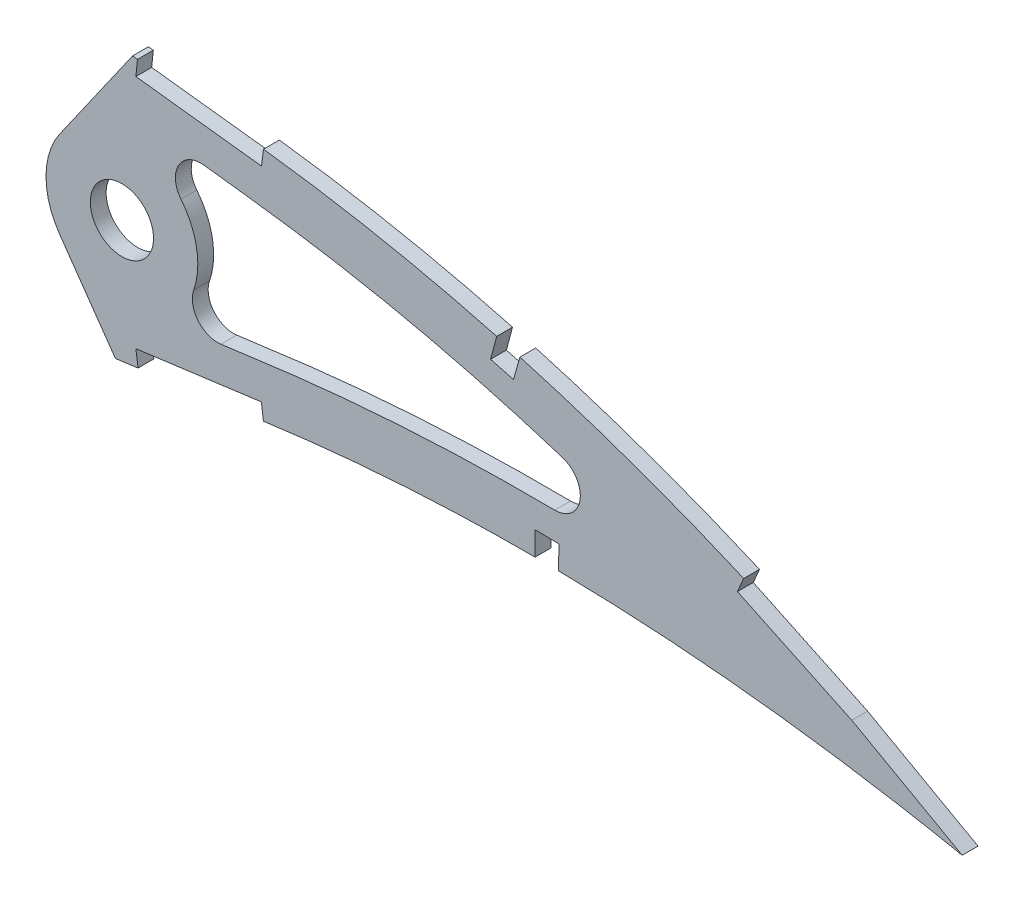
SolidWorks part; units mm, degrees
note: '?' marks a value the reader was unsure of.
material "Pine"
ref_plane "Front Plane" through (0, 0, 0) normal (0, 0, 1) x (1, 0, 0)
ref_plane "Top Plane" through (0, 0, 0) normal (0, 1, 0) x (1, 0, 0)
ref_plane "Right Plane" through (0, 0, 0) normal (1, 0, 0) x (0, 0, -1)
curve "Curve1"
  spline degree 3 poles (0, 0, 0) (0.1249, -0.5894, 0) (0.3751, -1.7709, 0) (1.0551, -3.4717, 0) (1.9543, -5.1067, 0) (3.0917, -6.6716, 0) (4.4597, -8.1658, 0) (6.0551, -9.5909, 0) (7.8766, -10.9463, 0) (9.9217, -12.2312, 0) (12.1874, -13.447, 0) (14.6712, -14.593, 0) (17.3708, -15.6688, 0) (20.2833, -16.6729, 0) (23.4051, -17.607, 0) (26.7332, -18.4687, 0) (30.2639, -19.2592, 0) (33.9938, -19.9766, 0) (37.9188, -20.6214, 0) (42.0348, -21.1935, 0) (46.3376, -21.6931, 0) (50.823, -22.1192, 0) (55.4866, -22.4726, 0) (60.3236, -22.7538, 0) (65.3294, -22.9634, 0) (70.4993, -23.1008, 0) (75.828, -23.1681, 0) (81.3109, -23.1662, 0) (86.9426, -23.0948, 0) (92.7182, -22.9577, 0) (98.6323, -22.754, 0) (104.6794, -22.4863, 0) (110.8541, -22.1572, 0) (117.1509, -21.7679, 0) (123.5642, -21.32, 0) (130.0885, -20.8172, 0) (136.7178, -20.2607, 0) (143.4464, -19.6538, 0) (150.2683, -18.9994, 0) (157.1776, -18.2998, 0) (164.1682, -17.5581, 0) (171.2339, -16.7767, 0) (178.3687, -15.9599, 0) (185.566, -15.1091, 0) (192.8198, -14.2292, 0) (200.1233, -13.3218, 0) (207.4703, -12.3905, 0) (214.8542, -11.4396, 0) (222.2681, -10.469, 0) (229.7058, -9.4856, 0) (237.1601, -8.4887, 0) (244.6246, -7.4833, 0) (252.0922, -6.4726, 0) (259.5558, -5.4569, 0) (267.0088, -4.4404, 0) (274.4442, -3.4259, 0) (281.8548, -2.4135, 0) (289.2339, -1.4081, 0) (296.574, -0.4098, 0) (303.8684, 0.5795, 0) (311.1101, 1.5569, 0) (318.2922, 2.521, 0) (325.4074, 3.4714, 0) (332.4485, 4.4082, 0) (339.3029, 5.3032, 0) (345.9529, 6.204, 0) (352.4207, 6.9424, 0) (358.808, 7.5727, 0) (365.1214, 8.0894, 0) (371.3533, 8.5001, 0) (377.4966, 8.8075, 0) (383.544, 9.0161, 0) (389.4878, 9.132, 0) (395.3205, 9.1582, 0) (401.0343, 9.1029, 0) (406.6218, 8.9708, 0) (412.075, 8.7675, 0) (417.3864, 8.5002, 0) (422.5485, 8.1759, 0) (427.5535, 7.7996, 0) (432.3944, 7.38, 0) (437.0637, 6.9232, 0) (441.5544, 6.4344, 0) (445.8598, 5.924, 0) (449.973, 5.3952, 0) (453.8879, 4.8568, 0) (457.5982, 4.3142, 0) (461.0979, 3.7743, 0) (464.3817, 3.2423, 0) (467.4441, 2.7253, 0) (470.2803, 2.228, 0) (472.8856, 1.7553, 0) (475.2562, 1.3133, 0) (477.3874, 0.904, 0) (479.2765, 0.5343, 0) (480.9199, 0.2058, 0) (482.3151, -0.077, 0) (483.4599, -0.3128, 0) (484.3523, -0.4979, 0) (484.9907, -0.6325, 0) (485.3743, -0.7125, 0) (485.5448, -0.7489, 0) (485.5874, -0.758, 0) knots 0 0 0 0 0.003638 0.007293 0.011028 0.014901 0.018963 0.023258 0.027821 0.032679 0.037853 0.043362 0.049215 0.055422 0.061989 0.068918 0.076211 0.083868 0.091887 0.100266 0.109 0.118085 0.127515 0.137285 0.147388 0.157816 0.168563 0.179619 0.190977 0.202627 0.21456 0.226767 0.239236 0.251959 0.264924 0.27812 0.291536 0.30516 0.318981 0.332985 0.347163 0.361499 0.375981 0.390597 0.405333 0.420175 0.43511 0.450124 0.465203 0.480333 0.495501 0.51069 0.525887 0.541078 0.556247 0.571382 0.586466 0.601485 0.616424 0.631269 0.646007 0.660621 0.675098 0.689423 0.703582 0.716908 0.730009 0.742952 0.755726 0.76832 0.780724 0.792927 0.804916 0.816679 0.828204 0.839475 0.850481 0.861208 0.871639 0.881763 0.891564 0.901027 0.910139 0.918884 0.927249 0.935221 0.942785 0.949928 0.956638 0.962904 0.968712 0.974054 0.978918 0.983297 0.98718 0.990561 0.993433 0.995791 0.99763 0.998946 0.999737 1 1 1 1
curve "Curve2"
  spline degree 3 poles (486.1938, 0.758, 0) (486.1565, 0.781, 0) (486.0077, 0.8729, 0) (485.6723, 1.0786, 0) (485.1139, 1.4213, 0) (484.3321, 1.8984, 0) (483.3276, 2.5088, 0) (482.0999, 3.2482, 0) (480.6498, 4.1141, 0) (478.9775, 5.1026, 0) (477.0833, 6.2089, 0) (474.9678, 7.4286, 0) (472.6313, 8.7548, 0) (470.0748, 10.182, 0) (467.2989, 11.7035, 0) (464.3043, 13.3123, 0) (461.0921, 15.0004, 0) (457.6635, 16.7605, 0) (454.019, 18.5827, 0) (450.1605, 20.4596, 0) (446.0892, 22.3819, 0) (441.8065, 24.3391, 0) (437.3149, 26.3234, 0) (432.6155, 28.3224, 0) (427.7112, 30.3274, 0) (422.6039, 32.3272, 0) (417.2967, 34.3124, 0) (411.7916, 36.2703, 0) (406.0928, 38.1924, 0) (400.203, 40.0661, 0) (394.1264, 41.8812, 0) (387.8666, 43.626, 0) (381.4288, 45.2916, 0) (374.8171, 46.8658, 0) (368.037, 48.3381, 0) (361.0939, 49.6996, 0) (353.9938, 50.9366, 0) (346.7562, 52.0484, 0) (339.4976, 52.9732, 0) (332.2539, 53.8802, 0) (325.021, 54.7322, 0) (317.6998, 55.5482, 0) (310.2971, 56.3235, 0) (302.8205, 57.0556, 0) (295.2774, 57.7415, 0) (287.6757, 58.3791, 0) (280.0227, 58.9648, 0) (272.3266, 59.4977, 0) (264.5949, 59.9731, 0) (256.8359, 60.3907, 0) (249.0573, 60.7475, 0) (241.2675, 61.0411, 0) (233.4745, 61.2698, 0) (225.6865, 61.4312, 0) (217.912, 61.5245, 0) (210.159, 61.547, 0) (202.4359, 61.4984, 0) (194.7508, 61.377, 0) (187.1122, 61.1811, 0) (179.5282, 60.9103, 0) (172.0069, 60.5649, 0) (164.5567, 60.1418, 0) (157.1855, 59.6438, 0) (149.9016, 59.0688, 0) (142.713, 58.4167, 0) (135.6273, 57.6901, 0) (128.6522, 56.887, 0) (121.7954, 56.0099, 0) (115.0642, 55.0603, 0) (108.4663, 54.0378, 0) (102.0087, 52.9453, 0) (95.6983, 51.784, 0) (89.542, 50.5572, 0) (83.5463, 49.2652, 0) (77.7176, 47.912, 0) (72.062, 46.4999, 0) (66.5855, 45.0315, 0) (61.2937, 43.5103, 0) (56.192, 41.9397, 0) (51.2862, 40.3215, 0) (46.5802, 38.6618, 0) (42.0796, 36.9619, 0) (37.788, 35.2268, 0) (33.7103, 33.4591, 0) (29.8497, 31.6641, 0) (26.2104, 29.8437, 0) (22.7951, 28.0033, 0) (19.6072, 26.1454, 0) (16.6497, 24.2737, 0) (13.924, 22.3929, 0) (11.4337, 20.504, 0) (9.1798, 18.612, 0) (7.1636, 16.7197, 0) (5.388, 14.8284, 0) (3.8531, 12.9414, 0) (2.5606, 11.0602, 0) (1.511, 9.1866, 0) (0.7066, 7.3219, 0) (0.1466, 5.4673, 0) (-0.16, 3.6254, 0) (-0.2363, 1.7948, 0) (-0.0786, 0.5974, 0) (0, 0, 0) knots 0 0 0 0 0.000254 0.001015 0.002283 0.004057 0.006331 0.009105 0.012374 0.016134 0.02038 0.025106 0.030306 0.035972 0.0421 0.048678 0.055702 0.06316 0.071046 0.07935 0.088063 0.097176 0.106678 0.116562 0.126814 0.137428 0.148394 0.1597 0.171338 0.183298 0.19557 0.208144 0.221012 0.234162 0.247587 0.261277 0.275223 0.289414 0.303771 0.317689 0.331784 0.34604 0.360444 0.374983 0.38964 0.404403 0.419257 0.434187 0.449177 0.464215 0.479284 0.49437 0.509458 0.524532 0.539579 0.554583 0.56953 0.584403 0.599191 0.613877 0.628447 0.642889 0.657186 0.671326 0.685294 0.699078 0.712665 0.726043 0.739198 0.752118 0.764792 0.777208 0.789356 0.801224 0.812804 0.824083 0.835055 0.84571 0.856038 0.866034 0.875689 0.884998 0.893953 0.902553 0.910789 0.918661 0.926166 0.933303 0.940071 0.946475 0.952518 0.958205 0.963547 0.968557 0.97325 0.977651 0.981787 0.985694 0.989415 0.993001 0.996508 1 1 1 1
sketch "Sketch1" plane through (0, 0, 0) normal (0, 0, 1) x (1, 0, 0)
  line L10 (485.5874, -0.758) -> (490.1477, -1.6846)
  line L24 (486.1938, 0.758) -> (490.1477, -1.6846)
  spline S2 degree 3 poles (-2903.3012, -752.343) (64.9845, 66.2759) (-8.319, 19.9761) (1.0551, -3.4717) (1.9543, -5.1067) (3.0917, -6.6716) (4.4597, -8.1658) (6.0551, -9.5909) (7.8766, -10.9463) (9.9217, -12.2312) (12.1874, -13.447) (14.6712, -14.593) (17.3708, -15.6688) (20.2833, -16.6729) (23.4051, -17.607) (26.7332, -18.4687) (30.2639, -19.2592) (33.9938, -19.9766) (37.9188, -20.6214) (42.0348, -21.1935) (46.3376, -21.6931) (50.823, -22.1192) (55.4866, -22.4726) (60.3236, -22.7538) (65.3294, -22.9634) (70.4993, -23.1008) (75.828, -23.1681) (81.3109, -23.1662) (86.9426, -23.0948) (92.7182, -22.9577) (98.6323, -22.754) (104.6794, -22.4863) (110.8541, -22.1572) (117.1509, -21.7679) (123.5642, -21.32) (130.0885, -20.8172) (136.7178, -20.2607) (143.4464, -19.6538) (150.2683, -18.9994) (157.1776, -18.2998) (164.1682, -17.5581) (171.2339, -16.7767) (178.3687, -15.9599) (185.566, -15.1091) (192.8198, -14.2292) (200.1233, -13.3218) (207.4703, -12.3905) (214.8542, -11.4396) (222.2681, -10.469) (229.7058, -9.4856) (237.1601, -8.4887) (244.6246, -7.4833) (252.0922, -6.4726) (259.5558, -5.4569) (267.0088, -4.4404) (274.4442, -3.4259) (281.8548, -2.4135) (289.2339, -1.4081) (296.574, -0.4098) (303.8684, 0.5795) (311.1101, 1.5569) (318.2922, 2.521) (325.4074, 3.4714) (332.4485, 4.4082) (339.3029, 5.3032) (345.9529, 6.204) (352.4207, 6.9424) (358.808, 7.5727) (365.1214, 8.0894) (371.3533, 8.5001) (377.4966, 8.8075) (383.544, 9.0161) (389.4878, 9.132) (395.3205, 9.1582) (401.0343, 9.1029) (406.6218, 8.9708) (412.075, 8.7675) (417.3864, 8.5002) (422.5485, 8.1759) (427.5535, 7.7996) (432.3944, 7.38) (437.0637, 6.9232) (441.5544, 6.4344) (445.8598, 5.924) (449.973, 5.3952) (453.8879, 4.8568) (457.5982, 4.3142) (461.0979, 3.7743) (464.3817, 3.2423) (467.4441, 2.7253) (470.2803, 2.228) (472.8856, 1.7553) (475.2562, 1.3133) (477.3874, 0.904) (479.2765, 0.5343) (480.9199, 0.2058) (482.3151, -0.077) (483.4599, -0.3128) (484.3523, -0.4979) (484.9907, -0.6325) (502.3108, -4.2475) (517.8244, -15.3527) (1156.8132, 2922.2173) knots -0.141005 -0.141005 -0.141005 -0.141005 0.003638 0.007293 0.011028 0.014901 0.018963 0.023258 0.027821 0.032679 0.037853 0.043362 0.049215 0.055422 0.061989 0.068918 0.076211 0.083868 0.091887 0.100266 0.109 0.118085 0.127515 0.137285 0.147388 0.157816 0.168563 0.179619 0.190977 0.202627 0.21456 0.226767 0.239236 0.251959 0.264924 0.27812 0.291536 0.30516 0.318981 0.332985 0.347163 0.361499 0.375981 0.390597 0.405333 0.420175 0.43511 0.450124 0.465203 0.480333 0.495501 0.51069 0.525887 0.541078 0.556247 0.571382 0.586466 0.601485 0.616424 0.631269 0.646007 0.660621 0.675098 0.689423 0.703582 0.716908 0.730009 0.742952 0.755726 0.76832 0.780724 0.792927 0.804916 0.816679 0.828204 0.839475 0.850481 0.861208 0.871639 0.881763 0.891564 0.901027 0.910139 0.918884 0.927249 0.935221 0.942785 0.949928 0.956638 0.962904 0.968712 0.974054 0.978918 0.983297 0.98718 0.990561 0.993433 0.995791 0.99763 0.998946 0.999737 1.104643 1.104643 1.104643 1.104643 only from (0, 0) to (485.5874, -0.758) construction
  spline S3 degree 3 poles (2108.3155, 2523.1468) (515.5269, -25.3358) (502.504, -9.2456) (485.6723, 1.0786) (485.1139, 1.4213) (484.3321, 1.8984) (483.3276, 2.5088) (482.0999, 3.2482) (480.6498, 4.1141) (478.9775, 5.1026) (477.0833, 6.2089) (474.9678, 7.4286) (472.6313, 8.7548) (470.0748, 10.182) (467.2989, 11.7035) (464.3043, 13.3123) (461.0921, 15.0004) (457.6635, 16.7605) (454.019, 18.5827) (450.1605, 20.4596) (446.0892, 22.3819) (441.8065, 24.3391) (437.3149, 26.3234) (432.6155, 28.3224) (427.7112, 30.3274) (422.6039, 32.3272) (417.2967, 34.3124) (411.7916, 36.2703) (406.0928, 38.1924) (400.203, 40.0661) (394.1264, 41.8812) (387.8666, 43.626) (381.4288, 45.2916) (374.8171, 46.8658) (368.037, 48.3381) (361.0939, 49.6996) (353.9938, 50.9366) (346.7562, 52.0484) (339.4976, 52.9732) (332.2539, 53.8802) (325.021, 54.7322) (317.6998, 55.5482) (310.2971, 56.3235) (302.8205, 57.0556) (295.2774, 57.7415) (287.6757, 58.3791) (280.0227, 58.9648) (272.3266, 59.4977) (264.5949, 59.9731) (256.8359, 60.3907) (249.0573, 60.7475) (241.2675, 61.0411) (233.4745, 61.2698) (225.6865, 61.4312) (217.912, 61.5245) (210.159, 61.547) (202.4359, 61.4984) (194.7508, 61.377) (187.1122, 61.1811) (179.5282, 60.9103) (172.0069, 60.5649) (164.5567, 60.1418) (157.1855, 59.6438) (149.9016, 59.0688) (142.713, 58.4167) (135.6273, 57.6901) (128.6522, 56.887) (121.7954, 56.0099) (115.0642, 55.0603) (108.4663, 54.0378) (102.0087, 52.9453) (95.6983, 51.784) (89.542, 50.5572) (83.5463, 49.2652) (77.7176, 47.912) (72.062, 46.4999) (66.5855, 45.0315) (61.2937, 43.5103) (56.192, 41.9397) (51.2862, 40.3215) (46.5802, 38.6618) (42.0796, 36.9619) (37.788, 35.2268) (33.7103, 33.4591) (29.8497, 31.6641) (26.2104, 29.8437) (22.7951, 28.0033) (19.6072, 26.1454) (16.6497, 24.2737) (13.924, 22.3929) (11.4337, 20.504) (9.1798, 18.612) (7.1636, 16.7197) (5.388, 14.8284) (3.8531, 12.9414) (2.5606, 11.0602) (1.511, 9.1866) (0.7066, 7.3219) (0.1466, 5.4673) (-0.16, 3.6254) (-1.2099, -21.5622) (83.495, -40.781) (-2988.1493, -256.3193) knots -0.112318 -0.112318 -0.112318 -0.112318 0.000254 0.001015 0.002283 0.004057 0.006331 0.009105 0.012374 0.016134 0.02038 0.025106 0.030306 0.035972 0.0421 0.048678 0.055702 0.06316 0.071046 0.07935 0.088063 0.097176 0.106678 0.116562 0.126814 0.137428 0.148394 0.1597 0.171338 0.183298 0.19557 0.208144 0.221012 0.234162 0.247587 0.261277 0.275223 0.289414 0.303771 0.317689 0.331784 0.34604 0.360444 0.374983 0.38964 0.404403 0.419257 0.434187 0.449177 0.464215 0.479284 0.49437 0.509458 0.524532 0.539579 0.554583 0.56953 0.584403 0.599191 0.613877 0.628447 0.642889 0.657186 0.671326 0.685294 0.699078 0.712665 0.726043 0.739198 0.752118 0.764792 0.777208 0.789356 0.801224 0.812804 0.824083 0.835055 0.84571 0.856038 0.866034 0.875689 0.884998 0.893953 0.902553 0.910789 0.918661 0.926166 0.933303 0.940071 0.946475 0.952518 0.958205 0.963547 0.968557 0.97325 0.977651 0.981787 0.985694 0.989415 0.993001 0.996508 1.135054 1.135054 1.135054 1.135054 only from (486.1938, 0.758) to (0, 0) construction
  spline S4 degree 3 poles (0, 0) (0.1249, -0.5894) (0.3751, -1.7709) (1.0551, -3.4717) (1.9543, -5.1067) (3.0917, -6.6716) (4.4597, -8.1658) (6.0551, -9.5909) (7.8766, -10.9463) (9.9217, -12.2312) (12.1874, -13.447) (14.6712, -14.593) (17.3708, -15.6688) (20.2833, -16.6729) (23.4051, -17.607) (26.7332, -18.4687) (30.2639, -19.2592) (33.9938, -19.9766) (37.9188, -20.6214) (42.0348, -21.1935) (46.3376, -21.6931) (50.823, -22.1192) (55.4866, -22.4726) (60.3236, -22.7538) (65.3294, -22.9634) (70.4993, -23.1008) (75.828, -23.1681) (81.3109, -23.1662) (86.9426, -23.0948) (92.7182, -22.9577) (98.6323, -22.754) (104.6794, -22.4863) (110.8541, -22.1572) (117.1509, -21.7679) (123.5642, -21.32) (130.0885, -20.8172) (136.7178, -20.2607) (143.4464, -19.6538) (150.2683, -18.9994) (157.1776, -18.2998) (164.1682, -17.5581) (171.2339, -16.7767) (178.3687, -15.9599) (185.566, -15.1091) (192.8198, -14.2292) (200.1233, -13.3218) (207.4703, -12.3905) (214.8542, -11.4396) (222.2681, -10.469) (229.7058, -9.4856) (237.1601, -8.4887) (244.6246, -7.4833) (252.0922, -6.4726) (259.5558, -5.4569) (267.0088, -4.4404) (274.4442, -3.4259) (281.8548, -2.4135) (289.2339, -1.4081) (296.574, -0.4098) (303.8684, 0.5795) (311.1101, 1.5569) (318.2922, 2.521) (325.4074, 3.4714) (332.4485, 4.4082) (339.3029, 5.3032) (345.9529, 6.204) (352.4207, 6.9424) (358.808, 7.5727) (365.1214, 8.0894) (371.3533, 8.5001) (377.4966, 8.8075) (383.544, 9.0161) (389.4878, 9.132) (395.3205, 9.1582) (401.0343, 9.1029) (406.6218, 8.9708) (412.075, 8.7675) (417.3864, 8.5002) (422.5485, 8.1759) (427.5535, 7.7996) (432.3944, 7.38) (437.0637, 6.9232) (441.5544, 6.4344) (445.8598, 5.924) (449.973, 5.3952) (453.8879, 4.8568) (457.5982, 4.3142) (461.0979, 3.7743) (464.3817, 3.2423) (467.4441, 2.7253) (470.2803, 2.228) (472.8856, 1.7553) (475.2562, 1.3133) (477.3874, 0.904) (479.2765, 0.5343) (480.9199, 0.2058) (482.3151, -0.077) (483.4599, -0.3128) (484.3523, -0.4979) (484.9907, -0.6325) (485.3743, -0.7125) (485.5448, -0.7489) (485.5874, -0.758) knots 0 0 0 0 0.003638 0.007293 0.011028 0.014901 0.018963 0.023258 0.027821 0.032679 0.037853 0.043362 0.049215 0.055422 0.061989 0.068918 0.076211 0.083868 0.091887 0.100266 0.109 0.118085 0.127515 0.137285 0.147388 0.157816 0.168563 0.179619 0.190977 0.202627 0.21456 0.226767 0.239236 0.251959 0.264924 0.27812 0.291536 0.30516 0.318981 0.332985 0.347163 0.361499 0.375981 0.390597 0.405333 0.420175 0.43511 0.450124 0.465203 0.480333 0.495501 0.51069 0.525887 0.541078 0.556247 0.571382 0.586466 0.601485 0.616424 0.631269 0.646007 0.660621 0.675098 0.689423 0.703582 0.716908 0.730009 0.742952 0.755726 0.76832 0.780724 0.792927 0.804916 0.816679 0.828204 0.839475 0.850481 0.861208 0.871639 0.881763 0.891564 0.901027 0.910139 0.918884 0.927249 0.935221 0.942785 0.949928 0.956638 0.962904 0.968712 0.974054 0.978918 0.983297 0.98718 0.990561 0.993433 0.995791 0.99763 0.998946 0.999737 1 1 1 1
  spline S5 degree 3 poles (486.1938, 0.758) (486.1565, 0.781) (486.0077, 0.8729) (485.6723, 1.0786) (485.1139, 1.4213) (484.3321, 1.8984) (483.3276, 2.5088) (482.0999, 3.2482) (480.6498, 4.1141) (478.9775, 5.1026) (477.0833, 6.2089) (474.9678, 7.4286) (472.6313, 8.7548) (470.0748, 10.182) (467.2989, 11.7035) (464.3043, 13.3123) (461.0921, 15.0004) (457.6635, 16.7605) (454.019, 18.5827) (450.1605, 20.4596) (446.0892, 22.3819) (441.8065, 24.3391) (437.3149, 26.3234) (432.6155, 28.3224) (427.7112, 30.3274) (422.6039, 32.3272) (417.2967, 34.3124) (411.7916, 36.2703) (406.0928, 38.1924) (400.203, 40.0661) (394.1264, 41.8812) (387.8666, 43.626) (381.4288, 45.2916) (374.8171, 46.8658) (368.037, 48.3381) (361.0939, 49.6996) (353.9938, 50.9366) (346.7562, 52.0484) (339.4976, 52.9732) (332.2539, 53.8802) (325.021, 54.7322) (317.6998, 55.5482) (310.2971, 56.3235) (302.8205, 57.0556) (295.2774, 57.7415) (287.6757, 58.3791) (280.0227, 58.9648) (272.3266, 59.4977) (264.5949, 59.9731) (256.8359, 60.3907) (249.0573, 60.7475) (241.2675, 61.0411) (233.4745, 61.2698) (225.6865, 61.4312) (217.912, 61.5245) (210.159, 61.547) (202.4359, 61.4984) (194.7508, 61.377) (187.1122, 61.1811) (179.5282, 60.9103) (172.0069, 60.5649) (164.5567, 60.1418) (157.1855, 59.6438) (149.9016, 59.0688) (142.713, 58.4167) (135.6273, 57.6901) (128.6522, 56.887) (121.7954, 56.0099) (115.0642, 55.0603) (108.4663, 54.0378) (102.0087, 52.9453) (95.6983, 51.784) (89.542, 50.5572) (83.5463, 49.2652) (77.7176, 47.912) (72.062, 46.4999) (66.5855, 45.0315) (61.2937, 43.5103) (56.192, 41.9397) (51.2862, 40.3215) (46.5802, 38.6618) (42.0796, 36.9619) (37.788, 35.2268) (33.7103, 33.4591) (29.8497, 31.6641) (26.2104, 29.8437) (22.7951, 28.0033) (19.6072, 26.1454) (16.6497, 24.2737) (13.924, 22.3929) (11.4337, 20.504) (9.1798, 18.612) (7.1636, 16.7197) (5.388, 14.8284) (3.8531, 12.9414) (2.5606, 11.0602) (1.511, 9.1866) (0.7066, 7.3219) (0.1466, 5.4673) (-0.16, 3.6254) (-0.2363, 1.7948) (-0.0786, 0.5974) (0, 0) knots 0 0 0 0 0.000254 0.001015 0.002283 0.004057 0.006331 0.009105 0.012374 0.016134 0.02038 0.025106 0.030306 0.035972 0.0421 0.048678 0.055702 0.06316 0.071046 0.07935 0.088063 0.097176 0.106678 0.116562 0.126814 0.137428 0.148394 0.1597 0.171338 0.183298 0.19557 0.208144 0.221012 0.234162 0.247587 0.261277 0.275223 0.289414 0.303771 0.317689 0.331784 0.34604 0.360444 0.374983 0.38964 0.404403 0.419257 0.434187 0.449177 0.464215 0.479284 0.49437 0.509458 0.524532 0.539579 0.554583 0.56953 0.584403 0.599191 0.613877 0.628447 0.642889 0.657186 0.671326 0.685294 0.699078 0.712665 0.726043 0.739198 0.752118 0.764792 0.777208 0.789356 0.801224 0.812804 0.824083 0.835055 0.84571 0.856038 0.866034 0.875689 0.884998 0.893953 0.902553 0.910789 0.918661 0.926166 0.933303 0.940071 0.946475 0.952518 0.958205 0.963547 0.968557 0.97325 0.977651 0.981787 0.985694 0.989415 0.993001 0.996508 1 1 1 1
extrude "Boss-Extrude1" add sketch "Sketch1" along normal blind 3.175
sketch "Sketch3" plane through (0, 0, 0) normal (0, 0, -1) x (-1, 0, 0)
  circle A0 centre (-312.3477, 26.2554) radius 6.35
  dimension "D1" = 12.7
  dimension "D2" = 177.8
  dimension "D3" = 27.94
extrude "Cut-Extrude2" cut sketch "Sketch3" against normal blind 7.62 contours A0
sketch "Sketch4" plane through (0, 0, 3.175) normal (0, 0, 1) x (1, 0, 0)
  line L0 (299.8639, 34.9967) -> (314.4881, 55.8824)
  line L1 (299.8639, 17.5141) -> (311.0441, 1.5471)
  line L2 (312.3477, 26.2554) -> (351.4914, 26.2554) construction
  line L3 (315.4787, 55.7778) -> (315.1439, 52.6205)
  line L4 (315.1439, 52.6205) -> (340.3707, 49.6596)
  line L5 (340.3707, 49.6596) -> (340.7711, 52.8093)
  line L6 (315.5809, 2.1568) -> (315.1587, 5.3036)
  line L7 (315.1587, 5.3036) -> (340.3373, 8.6498)
  line L8 (340.3373, 8.6498) -> (340.7575, 5.5027)
  line L9 (482.6749, 2.9016) -> (481.0376, 0.1814)
  line L10 (481.0376, 0.1814) -> (458.8647, 12.5718)
  line L11 (458.8647, 12.5718) -> (435.9153, 23.457)
  line L12 (435.9153, 23.457) -> (437.177, 26.3706)
  line L13 (458.8647, 12.5718) -> (460.3217, 15.3927)
  line L14 (387.5921, 43.6785) -> (386.3601, 39.0781)
  line L15 (386.3601, 39.0781) -> (390.9605, 37.8461)
  line L16 (390.9605, 37.8461) -> (392.2468, 42.3976)
  line L17 (395.3015, 9.1446) -> (395.3135, 13.9071)
  line L18 (395.3135, 13.9071) -> (400.0755, 13.8399)
  line L19 (400.0755, 13.8399) -> (400.0088, 9.1055)
  line L20 (437.177, 26.3706) -> (392.2468, 42.3976) construction
  line L21 (387.5921, 43.6785) -> (340.7711, 52.8093) construction
  line L22 (458.8647, 12.5718) -> (454.5015, 4.7638)
  line L23 (454.5015, 4.7638) -> (400.0088, 9.1055) construction
  line L24 (395.3015, 9.1446) -> (340.7575, 5.5027) construction
  circle A0 centre (312.3477, 26.2554) radius 6.35 construction
  circle A1 centre (312.3477, 26.2554) radius 6.35
  circle A2 centre (312.3477, 26.2554) radius 15.24
  arc A3 (324.2094, 35.8241) -> (328.7645, 44.0579) centre (328.1632, 39.0136) cw
  spline S0 degree 3 poles (-2903.3012, -752.343) (64.9845, 66.2759) (-8.319, 19.9761) (1.0551, -3.4717) (1.9543, -5.1067) (3.0917, -6.6716) (4.4597, -8.1658) (6.0551, -9.5909) (7.8766, -10.9463) (9.9217, -12.2312) (12.1874, -13.447) (14.6712, -14.593) (17.3708, -15.6688) (20.2833, -16.6729) (23.4051, -17.607) (26.7332, -18.4687) (30.2639, -19.2592) (33.9938, -19.9766) (37.9188, -20.6214) (42.0348, -21.1935) (46.3376, -21.6931) (50.823, -22.1192) (55.4866, -22.4726) (60.3236, -22.7538) (65.3294, -22.9634) (70.4993, -23.1008) (75.828, -23.1681) (81.3109, -23.1662) (86.9426, -23.0948) (92.7182, -22.9577) (98.6323, -22.754) (104.6794, -22.4863) (110.8541, -22.1572) (117.1509, -21.7679) (123.5642, -21.32) (130.0885, -20.8172) (136.7178, -20.2607) (143.4464, -19.6538) (150.2683, -18.9994) (157.1776, -18.2998) (164.1682, -17.5581) (171.2339, -16.7767) (178.3687, -15.9599) (185.566, -15.1091) (192.8198, -14.2292) (200.1233, -13.3218) (207.4703, -12.3905) (214.8542, -11.4396) (222.2681, -10.469) (229.7058, -9.4856) (237.1601, -8.4887) (244.6246, -7.4833) (252.0922, -6.4726) (259.5558, -5.4569) (267.0088, -4.4404) (274.4442, -3.4259) (281.8548, -2.4135) (289.2339, -1.4081) (296.574, -0.4098) (303.8684, 0.5795) (311.1101, 1.5569) (318.2922, 2.521) (325.4074, 3.4714) (332.4485, 4.4082) (339.3029, 5.3032) (345.9529, 6.204) (352.4207, 6.9424) (358.808, 7.5727) (365.1214, 8.0894) (371.3533, 8.5001) (377.4966, 8.8075) (383.544, 9.0161) (389.4878, 9.132) (395.3205, 9.1582) (401.0343, 9.1029) (406.6218, 8.9708) (412.075, 8.7675) (417.3864, 8.5002) (422.5485, 8.1759) (427.5535, 7.7996) (432.3944, 7.38) (437.0637, 6.9232) (441.5544, 6.4344) (445.8598, 5.924) (449.973, 5.3952) (453.8879, 4.8568) (457.5982, 4.3142) (461.0979, 3.7743) (464.3817, 3.2423) (467.4441, 2.7253) (470.2803, 2.228) (472.8856, 1.7553) (475.2562, 1.3133) (477.3874, 0.904) (479.2765, 0.5343) (480.9199, 0.2058) (482.3151, -0.077) (483.4599, -0.3128) (484.3523, -0.4979) (484.9907, -0.6325) (502.3108, -4.2475) (517.8244, -15.3527) (1156.8132, 2922.2173) knots -0.141005 -0.141005 -0.141005 -0.141005 0.003638 0.007293 0.011028 0.014901 0.018963 0.023258 0.027821 0.032679 0.037853 0.043362 0.049215 0.055422 0.061989 0.068918 0.076211 0.083868 0.091887 0.100266 0.109 0.118085 0.127515 0.137285 0.147388 0.157816 0.168563 0.179619 0.190977 0.202627 0.21456 0.226767 0.239236 0.251959 0.264924 0.27812 0.291536 0.30516 0.318981 0.332985 0.347163 0.361499 0.375981 0.390597 0.405333 0.420175 0.43511 0.450124 0.465203 0.480333 0.495501 0.51069 0.525887 0.541078 0.556247 0.571382 0.586466 0.601485 0.616424 0.631269 0.646007 0.660621 0.675098 0.689423 0.703582 0.716908 0.730009 0.742952 0.755726 0.76832 0.780724 0.792927 0.804916 0.816679 0.828204 0.839475 0.850481 0.861208 0.871639 0.881763 0.891564 0.901027 0.910139 0.918884 0.927249 0.935221 0.942785 0.949928 0.956638 0.962904 0.968712 0.974054 0.978918 0.983297 0.98718 0.990561 0.993433 0.995791 0.99763 0.998946 0.999737 1.104643 1.104643 1.104643 1.104643 only from (0, 0) to (485.5874, -0.758) construction
  spline S1 degree 3 poles (2108.3155, 2523.1468) (515.5269, -25.3358) (502.504, -9.2456) (485.6723, 1.0786) (485.1139, 1.4213) (484.3321, 1.8984) (483.3276, 2.5088) (482.0999, 3.2482) (480.6498, 4.1141) (478.9775, 5.1026) (477.0833, 6.2089) (474.9678, 7.4286) (472.6313, 8.7548) (470.0748, 10.182) (467.2989, 11.7035) (464.3043, 13.3123) (461.0921, 15.0004) (457.6635, 16.7605) (454.019, 18.5827) (450.1605, 20.4596) (446.0892, 22.3819) (441.8065, 24.3391) (437.3149, 26.3234) (432.6155, 28.3224) (427.7112, 30.3274) (422.6039, 32.3272) (417.2967, 34.3124) (411.7916, 36.2703) (406.0928, 38.1924) (400.203, 40.0661) (394.1264, 41.8812) (387.8666, 43.626) (381.4288, 45.2916) (374.8171, 46.8658) (368.037, 48.3381) (361.0939, 49.6996) (353.9938, 50.9366) (346.7562, 52.0484) (339.4976, 52.9732) (332.2539, 53.8802) (325.021, 54.7322) (317.6998, 55.5482) (310.2971, 56.3235) (302.8205, 57.0556) (295.2774, 57.7415) (287.6757, 58.3791) (280.0227, 58.9648) (272.3266, 59.4977) (264.5949, 59.9731) (256.8359, 60.3907) (249.0573, 60.7475) (241.2675, 61.0411) (233.4745, 61.2698) (225.6865, 61.4312) (217.912, 61.5245) (210.159, 61.547) (202.4359, 61.4984) (194.7508, 61.377) (187.1122, 61.1811) (179.5282, 60.9103) (172.0069, 60.5649) (164.5567, 60.1418) (157.1855, 59.6438) (149.9016, 59.0688) (142.713, 58.4167) (135.6273, 57.6901) (128.6522, 56.887) (121.7954, 56.0099) (115.0642, 55.0603) (108.4663, 54.0378) (102.0087, 52.9453) (95.6983, 51.784) (89.542, 50.5572) (83.5463, 49.2652) (77.7176, 47.912) (72.062, 46.4999) (66.5855, 45.0315) (61.2937, 43.5103) (56.192, 41.9397) (51.2862, 40.3215) (46.5802, 38.6618) (42.0796, 36.9619) (37.788, 35.2268) (33.7103, 33.4591) (29.8497, 31.6641) (26.2104, 29.8437) (22.7951, 28.0033) (19.6072, 26.1454) (16.6497, 24.2737) (13.924, 22.3929) (11.4337, 20.504) (9.1798, 18.612) (7.1636, 16.7197) (5.388, 14.8284) (3.8531, 12.9414) (2.5606, 11.0602) (1.511, 9.1866) (0.7066, 7.3219) (0.1466, 5.4673) (-0.16, 3.6254) (-1.2099, -21.5622) (83.495, -40.781) (-2988.1493, -256.3193) knots -0.112318 -0.112318 -0.112318 -0.112318 0.000254 0.001015 0.002283 0.004057 0.006331 0.009105 0.012374 0.016134 0.02038 0.025106 0.030306 0.035972 0.0421 0.048678 0.055702 0.06316 0.071046 0.07935 0.088063 0.097176 0.106678 0.116562 0.126814 0.137428 0.148394 0.1597 0.171338 0.183298 0.19557 0.208144 0.221012 0.234162 0.247587 0.261277 0.275223 0.289414 0.303771 0.317689 0.331784 0.34604 0.360444 0.374983 0.38964 0.404403 0.419257 0.434187 0.449177 0.464215 0.479284 0.49437 0.509458 0.524532 0.539579 0.554583 0.56953 0.584403 0.599191 0.613877 0.628447 0.642889 0.657186 0.671326 0.685294 0.699078 0.712665 0.726043 0.739198 0.752118 0.764792 0.777208 0.789356 0.801224 0.812804 0.824083 0.835055 0.84571 0.856038 0.866034 0.875689 0.884998 0.893953 0.902553 0.910789 0.918661 0.926166 0.933303 0.940071 0.946475 0.952518 0.958205 0.963547 0.968557 0.97325 0.977651 0.981787 0.985694 0.989415 0.993001 0.996508 1.135054 1.135054 1.135054 1.135054 only from (486.1938, 0.758) to (0, 0) construction
  spline S2 degree 3 poles (175.8391, -16.2481) (176.6748, -16.152) (179.9112, -15.7776) (185.566, -15.1091) (192.8198, -14.2292) (200.1233, -13.3218) (207.4703, -12.3905) (214.8542, -11.4396) (222.2681, -10.469) (229.7058, -9.4856) (237.1601, -8.4887) (244.6246, -7.4833) (252.0922, -6.4726) (259.5558, -5.4569) (267.0088, -4.4404) (274.4442, -3.4259) (281.8548, -2.4135) (289.2339, -1.4081) (296.574, -0.4098) (303.8684, 0.5795) (311.1101, 1.5569) (318.2922, 2.521) (325.4074, 3.4714) (332.4485, 4.4082) (339.3029, 5.3032) (345.9529, 6.204) (352.4207, 6.9424) (358.808, 7.5727) (365.1214, 8.0894) (371.3533, 8.5001) (377.4966, 8.8075) (383.544, 9.0161) (389.4878, 9.132) (395.3205, 9.1582) (401.0343, 9.1029) (406.6218, 8.9708) (412.075, 8.7675) (417.3864, 8.5002) (422.5485, 8.1759) (427.5535, 7.7996) (432.3944, 7.38) (437.0637, 6.9232) (441.5544, 6.4344) (445.8598, 5.924) (449.973, 5.3952) (453.8879, 4.8568) (457.5982, 4.3142) (461.0979, 3.7743) (464.3817, 3.2423) (467.4441, 2.7253) (470.2803, 2.228) (472.8856, 1.7553) (475.2562, 1.3133) (477.3874, 0.904) (479.2765, 0.5343) (480.9199, 0.2058) (482.3151, -0.077) (483.4599, -0.3128) (484.3523, -0.4979) (484.9907, -0.6325) (485.3743, -0.7125) (485.5448, -0.7489) (485.5874, -0.758) knots 0.370893 0.370893 0.370893 0.370893 0.375981 0.390597 0.405333 0.420175 0.43511 0.450124 0.465203 0.480333 0.495501 0.51069 0.525887 0.541078 0.556247 0.571382 0.586466 0.601485 0.616424 0.631269 0.646007 0.660621 0.675098 0.689423 0.703582 0.716908 0.730009 0.742952 0.755726 0.76832 0.780724 0.792927 0.804916 0.816679 0.828204 0.839475 0.850481 0.861208 0.871639 0.881763 0.891564 0.901027 0.910139 0.918884 0.927249 0.935221 0.942785 0.949928 0.956638 0.962904 0.968712 0.974054 0.978918 0.983297 0.98718 0.990561 0.993433 0.995791 0.99763 0.998946 0.999737 1 1 1 1
  spline S3 degree 3 poles (486.1938, 0.758) (486.1565, 0.781) (486.0077, 0.8729) (485.6723, 1.0786) (485.1139, 1.4213) (484.3321, 1.8984) (483.3276, 2.5088) (482.0999, 3.2482) (480.6498, 4.1141) (478.9775, 5.1026) (477.0833, 6.2089) (474.9678, 7.4286) (472.6313, 8.7548) (470.0748, 10.182) (467.2989, 11.7035) (464.3043, 13.3123) (461.0921, 15.0004) (457.6635, 16.7605) (454.019, 18.5827) (450.1605, 20.4596) (446.0892, 22.3819) (441.8065, 24.3391) (437.3149, 26.3234) (432.6155, 28.3224) (427.7112, 30.3274) (422.6039, 32.3272) (417.2967, 34.3124) (411.7916, 36.2703) (406.0928, 38.1924) (400.203, 40.0661) (394.1264, 41.8812) (387.8666, 43.626) (381.4288, 45.2916) (374.8171, 46.8658) (368.037, 48.3381) (361.0939, 49.6996) (353.9938, 50.9366) (346.7562, 52.0484) (339.4976, 52.9732) (332.2539, 53.8802) (325.021, 54.7322) (317.6998, 55.5482) (310.2971, 56.3235) (302.8205, 57.0556) (295.2774, 57.7415) (287.6757, 58.3791) (280.0227, 58.9648) (272.3266, 59.4977) (264.5949, 59.9731) (256.8359, 60.3907) (249.0573, 60.7475) (241.2675, 61.0411) (233.4745, 61.2698) (225.6865, 61.4312) (217.912, 61.5245) (210.159, 61.547) (202.4359, 61.4984) (194.7508, 61.377) (187.1122, 61.1811) (179.5282, 60.9103) (172.9572, 60.6085) (168.9158, 60.3874) (167.3814, 60.2983) knots 0 0 0 0 0.000254 0.001015 0.002283 0.004057 0.006331 0.009105 0.012374 0.016134 0.02038 0.025106 0.030306 0.035972 0.0421 0.048678 0.055702 0.06316 0.071046 0.07935 0.088063 0.097176 0.106678 0.116562 0.126814 0.137428 0.148394 0.1597 0.171338 0.183298 0.19557 0.208144 0.221012 0.234162 0.247587 0.261277 0.275223 0.289414 0.303771 0.317689 0.331784 0.34604 0.360444 0.374983 0.38964 0.404403 0.419257 0.434187 0.449177 0.464215 0.479284 0.49437 0.509458 0.524532 0.539579 0.554583 0.56953 0.584403 0.599191 0.613877 0.628447 0.637368 0.637368 0.637368 0.637368
  spline S4 degree 1 poles (480.8541, -7.8857) (167.9703, 50.1554) knots 0 0 1 1 construction
  spline S5 degree 3 poles (480.8541, -7.8857) (480.6807, -7.7786) (480.3384, -7.5686) (479.6124, -7.1234) (478.3653, -6.3632) (475.8643, -4.8551) (470.8166, -1.8777) (460.6292, 3.8683) (439.8101, 14.5473) (415.1044, 24.7558) (389.6644, 32.7731) (373.4973, 36.841) (360.4548, 39.5066) (350.5756, 41.2283) (342.4188, 42.3688) (335.8615, 43.1889) (332.3125, 43.6295) (329.6081, 43.9577) (325.9864, 44.3892) (319.4013, 45.1439) (306.8956, 46.4826) (289.9681, 48.0541) (269.632, 49.549) (242.4959, 50.9921) (208.5547, 51.7044) (181.489, 50.9403) (167.9703, 50.1554) knots 0 0 0 0 0.001245 0.00249 0.004979 0.009959 0.019918 0.039835 0.079671 0.159342 0.199177 0.239013 0.258931 0.278848 0.298766 0.308725 0.317223 0.319712 0.324692 0.338602 0.358519 0.398355 0.43819 0.478026 0.557697 0.637368 0.637368 0.637368 0.637368
  spline S6 degree 1 poles (174.6781, -6.1547) (487.707, 9.1785) knots 0 0 1 1 construction
  spline S7 degree 3 poles (174.6781, -6.1547) (187.5459, -4.6746) (213.2294, -1.4637) (245.4074, 2.865) (271.1631, 6.3806) (290.492, 9.0192) (306.6078, 11.2053) (319.5106, 12.9344) (327.5638, 14.0105) (334.0433, 14.8623) (338.8265, 15.4927) (343.7157, 16.1512) (350.3986, 16.9529) (358.6595, 17.783) (371.9753, 18.7921) (388.6327, 19.4303) (408.6348, 19.217) (428.5831, 18.0526) (448.4396, 15.98) (464.869, 13.5352) (476.3098, 11.471) (482.0033, 10.3548) (484.8453, 9.7758) (486.2719, 9.4806) (486.9827, 9.3308) (487.3675, 9.2505) (487.5969, 9.2019) (487.707, 9.1785) knots 0.370893 0.370893 0.370893 0.370893 0.449531 0.528169 0.567489 0.606808 0.646127 0.665787 0.685446 0.695276 0.705106 0.714936 0.724766 0.744425 0.764085 0.803404 0.842723 0.882042 0.921362 0.960681 0.98034 0.99017 0.995085 0.997543 0.998771 0.999386 1 1 1 1
  dimension "D1" = 30.48
  dimension "D8" = 5.08
  dimension "D2" = 55
  dimension "D3" = 55
  dimension "D4" = 3.175
  dimension "D5" = 25.4
  dimension "D6" = 4.7625
  dimension "D7" = 10.16
extrude "Cut-Extrude3" cut sketch "Sketch4" against normal through all
ref_axis "Axis1" through (312.3477, 26.2554, 3.175) along (0, 0, -1)?
fillet "Fillet1" radius 5.08 2 edges at (319.825, 12.9758, 1.5875) (431.7907, 17.6272, 1.5875)
